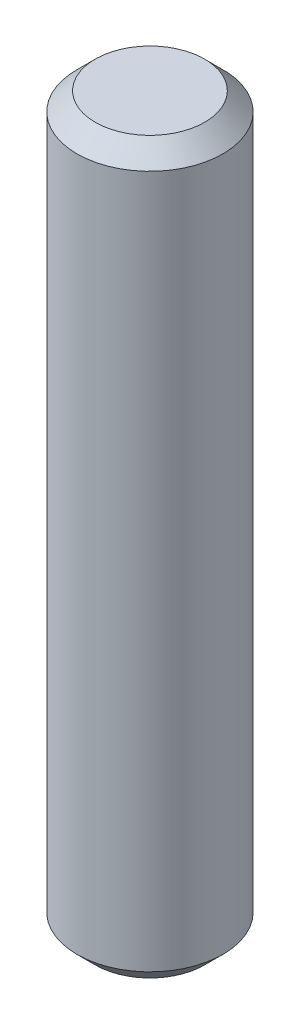
SolidWorks part; units mm, degrees
ref_plane "Front Plane" through (0, 0, 0) normal (0, 0, 1) x (1, 0, 0)
ref_plane "Top Plane" through (0, 0, 0) normal (0, 1, 0) x (1, 0, 0)
ref_plane "Right Plane" through (0, 0, 0) normal (1, 0, 0) x (0, 0, -1)
sketch "Sketch1" plane through (0, 0, 0) normal (0, 1, 0) x (1, 0, 0)
  circle A0 centre (0, 0) radius 2
extrude "Boss-Extrude1" add sketch "Sketch1" along normal blind 20
chamfer "Chamfer1" distance 0.5 angle 45 2 edges at (0, 0, 2) (0, 20, 2)
